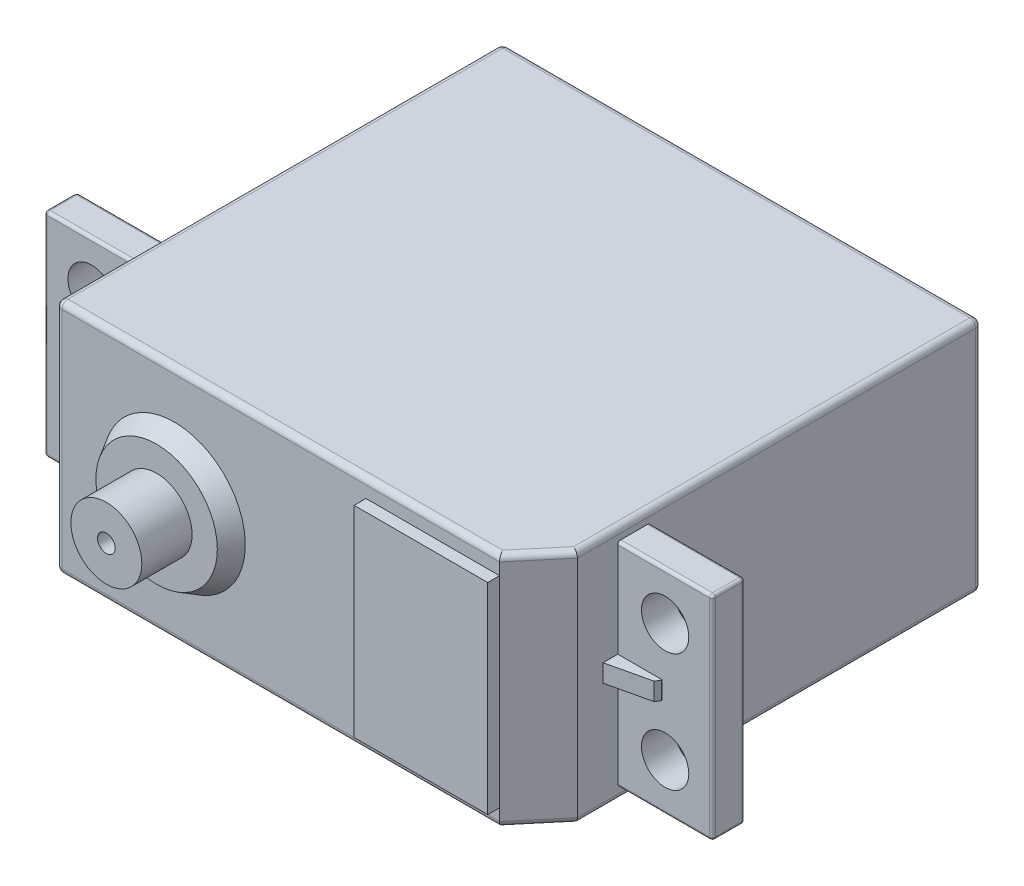
SolidWorks part; units mm, degrees
ref_plane "Front Plane" through (0, 0, 0) normal (0, 0, 1) x (1, 0, 0)
ref_plane "Top Plane" through (0, 0, 0) normal (0, 1, 0) x (1, 0, 0)
ref_plane "Right Plane" through (0, 0, 0) normal (1, 0, 0) x (0, 0, -1)
sketch "Sketch1" plane through (0, 0, 0) normal (0, 0, 1) x (1, 0, 0)
  line L1 (-20.25, -10) -> (20.25, -10)
  line L2 (-20.25, -10) -> (-20.25, 10)
  line L3 (-20.25, 10) -> (20.25, 10)
  line L4 (20.25, -10) -> (20.25, 10)
  line L5 (-20.25, -10) -> (20.25, 10) construction
  line L6 (-20.25, 10) -> (20.25, -10) construction
  point P0 (0, 0)
  dimension "D1" = 40.5
  dimension "D2" = 20
extrude "Boss-Extrude1" add sketch "Sketch1" along normal blind 37.75
sketch "Sketch2" plane through (20.25, 0, 0) normal (1, 0, 0) x (0, 0, -1)
  line L0 (-37.75, -10) -> (-37.75, 10) construction
  line L1 (-30.75, 9) -> (-28, 9)
  line L2 (-30.75, 9) -> (-30.75, -9)
  line L3 (-30.75, -9) -> (-28, -9)
  line L4 (-28, 9) -> (-28, -9)
  line L5 (-37.75, -10) -> (0, -10) construction
  dimension "D1" = 7
  dimension "D2" = 2.75
  dimension "D3" = 18
  dimension "D4" = 1
extrude "Boss-Extrude2" add sketch "Sketch2" along normal blind 8
sketch "Sketch3" plane through (0, 0, 30.75) normal (0, 0, 1) x (1, 0, 0)
  line L0 (24.25, 9) -> (24.25, -9) construction
  line L1 (28.25, 9) -> (20.25, 9) construction
  line L2 (28.25, -9) -> (20.25, -9) construction
  line L3 (24.25, 0) -> (28.25, 0) construction
  line L5 (28.25, 9) -> (28.25, -9) construction
  circle A0 centre (24.25, 5) radius 2
  circle A1 centre (24.25, -5) radius 2
  circle A2 centre (24.25, 0) radius 5 construction
  dimension "D1" = 4
  dimension "D2" = 10
extrude "Cut-Extrude1" cut sketch "Sketch3" against normal blind 4
sketch "Sketch4" plane through (0, 0, 30.75) normal (0, 0, 1) x (1, 0, 0)
  line L0 (28.25, 0) -> (20.25, 0) construction
  line L1 (28.25, 9) -> (28.25, -9) construction
  line L2 (20.25, -10) -> (20.25, 10) construction
  line L3 (20.25, 0) -> (24, 0) construction
  line L4 (20.25, -0.75) -> (24, -0.75)
  line L5 (20.25, 0.75) -> (24, 0.75)
  line L6 (20.25, -0.75) -> (20.25, 0.75)
  line L7 (24, -0.75) -> (24, 0.75)
  dimension "D1" = 3.75
  dimension "D2" = 0.75
  dimension "D3" = 0.75
extrude "Boss-Extrude3" add sketch "Sketch4" along normal blind 1.25
chamfer "Chamfer1" distance 3.75 angle 13 1 edges at (24, 0, 32)
chamfer "Chamfer2" distance 0.25 angle 45 1 edges at (24, 0, 31.1342)
fillet "Fillet1" radius 0.25 8 edges at (24.25, -9, 28) (28.25, 0, 28) (24.25, 9, 28) (28.25, 9, 29.375) (28.25, -9, 29.375) (24.25, -9, 30.75) (28.25, 0, 30.75) (24.25, 9, 30.75)
mirror "Mirror1" about plane through (0, 0, 0) normal (1, 0, 0) of "Boss-Extrude2", "Cut-Extrude1", "Boss-Extrude3", "Chamfer1", "Chamfer2", "Fillet1"
sketch "Sketch5" plane through (0, 0, 37.75) normal (0, 0, 1) x (1, 0, 0)
  line L0 (20.25, -10) -> (20.25, 10) construction
  line L1 (5.95, 8.5) -> (17.25, 8.5)
  line L2 (5.95, 8.5) -> (5.95, -8.5)
  line L3 (5.95, -8.5) -> (17.25, -8.5)
  line L4 (17.25, 8.5) -> (17.25, -8.5)
  line L5 (-20.25, -10) -> (20.25, -10) construction
  dimension "D1" = 3
  dimension "D2" = 11.3
  dimension "D3" = 17
  dimension "D4" = 1.5
extrude "Boss-Extrude4" add sketch "Sketch5" along normal blind 1
sketch "Sketch6" plane through (0, 0, 37.75) normal (0, 0, 1) x (1, 0, 0)
  line L0 (-20.25, 10) -> (-20.25, -10) construction
  line L1 (-10.25, 10) -> (-10.25, -10) construction
  line L2 (20.25, 10) -> (-20.25, 10) construction
  line L3 (-20.25, -10) -> (20.25, -10) construction
  circle A0 centre (-10.25, 0) radius 6
  dimension "D1" = 12
  dimension "D2" = 10
extrude "Boss-Extrude5" add sketch "Sketch6" along normal blind 1.5
chamfer "Chamfer3" distance 1.5 angle 30 1 edges at (-4.25, 0, 39.25)
sketch "Sketch7" plane through (0, 0, 39.25) normal (0, 0, 1) x (1, 0, 0)
  circle A0 centre (-10.25, 0) radius 3
  circle A1 centre (-10.25, 0) radius 0.75
  dimension "D1" = 6
  dimension "D2" = 1.5
extrude "Boss-Extrude6" add sketch "Sketch7" along normal blind 4.25
sketch "Sketch8" plane through (-20.25, 0, 0) normal (-1, 0, 0) x (0, 0, 1)
  line L0 (0, 10) -> (0, -10) construction
  line L1 (1.5, 3.625) -> (4.75, 3.625)
  line L2 (1.5, 3.625) -> (1.5, -3.625)
  line L3 (1.5, -3.625) -> (4.75, -3.625)
  line L4 (4.75, 3.625) -> (4.75, -3.625)
  line L5 (1.5, 0) -> (4.75, 0) construction
  line L6 (3.125, 10) -> (3.125, -10) construction
  line L7 (37.75, 10) -> (0, 10) construction
  line L8 (37.75, -10) -> (0, -10) construction
  line L9 (3.75, 2.625) -> (3.75, -2.625)
  line L10 (2.5, -2.625) -> (3.75, -2.625)
  line L11 (2.5, 2.625) -> (2.5, -2.625)
  line L12 (2.5, 2.625) -> (3.75, 2.625)
  point P14 (3.125, 0)
  dimension "D1" = 1.5
  dimension "D2" = 3.25
  dimension "D3" = 7.25
  dimension "D4" = 1
extrude "Boss-Extrude7" add sketch "Sketch8" along normal blind 2.5
chamfer "Chamfer5" distance 3 angle 50 1 edges at (20.25, 0, 37.75)
chamfer "Chamfer4" distance 2.5 angle 15 4 edges at (-22.75, -3.625, 3.125) (-22.75, 0, 4.75) (-22.75, 3.625, 3.125) (-22.75, 0, 1.5)
fillet "Fillet2" radius 0.5 13 edges at (20.25, 10, 17.0874) (-1.5, 10, 37.75) (-1.5, -10, 37.75) (20.25, -10, 17.0874) (20.25, 0, 0) (0, -10, 0) (0, 10, 0) (-20.25, 0, 0) (-20.25, 10, 18.875) (-20.25, -10, 18.875) (-20.25, 0, 37.75) (18.75, -10, 35.9624) (18.75, 10, 35.9624)
